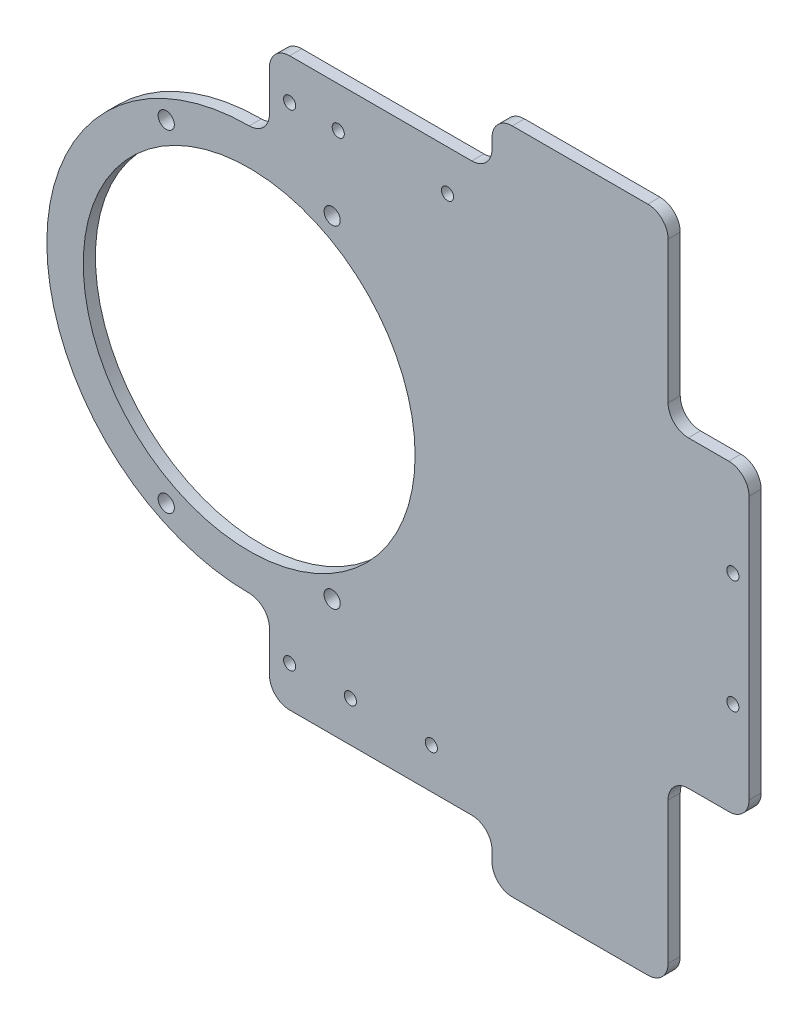
SolidWorks part; units mm, degrees
ref_plane "前视基准面" through (0, 0, 0) normal (0, 0, 1) x (1, 0, 0)
ref_plane "上视基准面" through (0, 0, 0) normal (0, 1, 0) x (1, 0, 0)
ref_plane "右视基准面" through (0, 0, 0) normal (1, 0, 0) x (0, 0, -1)
other "Configuration Table"
sketch "草图1" plane through (0, 0, 0) normal (0, 0, 1) x (1, 0, 0)
  line L1 (-55, 50) -> (55, 50)
  line L2 (-55, 50) -> (-55, -50)
  line L3 (-55, -50) -> (55, -50)
  line L4 (55, 50) -> (55, -50)
  line L5 (-55, 50) -> (55, -50) construction
  line L6 (-55, -50) -> (55, 50) construction
  line L7 (118.5, 82.5) -> (55, 82.5)
  line L8 (118.5, 82.5) -> (118.5, -82.5)
  line L9 (118.5, -82.5) -> (55, -82.5)
  line L10 (55, 82.5) -> (55, -82.5)
  line L11 (118.5, 82.5) -> (55, -82.5) construction
  line L12 (118.5, -82.5) -> (55, 82.5) construction
  line L21 (55, 50) -> (0, 50)
  line L22 (55, 50) -> (55, 70)
  line L23 (55, 70) -> (0, 70)
  line L24 (0, 50) -> (0, 70)
  line L25 (55, -50) -> (0, -50)
  line L26 (55, -50) -> (55, -70)
  line L27 (55, -70) -> (0, -70)
  line L28 (0, -50) -> (0, -70)
  point P0 (0, 0)
  point P6 (86.75, 0)
  dimension "D1" = 100
  dimension "D2" = 110
  dimension "D3" = 173.5
  dimension "D4" = 165
  dimension "D9" = 20
  dimension "D10" = 20
  dimension "D11" = 55
  dimension "D12" = 55
extrude "凸台-拉伸1" add sketch "草图1" along normal blind 3 contours L4 L1 L2 L3 | L7 L10 L4 L9 L8 | L8 | L8 | L24 L1 L10 L23 | L3 L28 L27 L10 region at (0, 0, 0) region at (27.5, 60, 0) region at (86.75, 0, 0) region at (27.5, -60, 0)
fillet "圆角1" radius 50 2 edges at (-55, -50, 1.5) (-55, 50, 1.5)
sketch "草图2" plane through (0, 0, 3) normal (0, 0, 1) x (1, 0, 0)
  circle A0 centre (-5, 0) radius 41
  dimension "D1" = 82
extrude "切除-拉伸1" cut sketch "草图2" against normal blind 10
fillet "圆角4" radius 5 6 edges at (0, 70, 1.5) (55, 70, 1.5) (55, -70, 1.5) (0, -70, 1.5) (0, -50, 1.5) (0, 50, 1.5)
sketch "草图3" plane through (0, 0, 3) normal (0, 0, 1) x (1, 0, 0)
  line L1 (0, -55) -> (0, -65) construction
  line L2 (-25.5, -41) -> (15.5, -41) construction
  line L3 (-25.5, -41) -> (-25.5, 41) construction
  line L4 (-25.5, 41) -> (15.5, 41) construction
  line L5 (15.5, -41) -> (15.5, 41) construction
  line L6 (-25.5, -41) -> (15.5, 41) construction
  line L7 (-25.5, 41) -> (15.5, -41) construction
  line L8 (50, -70) -> (5, -70) construction
  line L9 (0, 55) -> (0, 65) construction
  line L10 (50, 70) -> (5, 70) construction
  line L11 (118.5, 82.5) -> (118.5, -82.5) construction
  circle A0 centre (114.5, 14) radius 1.5
  circle A1 centre (114.5, -14) radius 1.5
  circle A2 centre (-5, 0) radius 41 construction
  circle A3 centre (-5, 0) radius 41 construction
  circle A4 centre (-25.5, 41) radius 2
  circle A5 centre (15.5, 41) radius 2
  circle A6 centre (15.5, -41) radius 2
  circle A7 centre (-25.5, -41) radius 2
  circle A8 centre (5, -60) radius 1.5
  circle A9 centre (20, -60) radius 1.5
  circle A10 centre (40, -60) radius 1.5
  circle A11 centre (5, 60) radius 1.5
  circle A12 centre (17, 60) radius 1.5
  circle A13 centre (44, 60) radius 1.5
  dimension "D3" = 3
  dimension "D4" = 3
  dimension "D8" = 4
  dimension "D9" = 4
  dimension "D10" = 4
  dimension "D11" = 4
  dimension "D12" = 3
  dimension "D13" = 3
  dimension "D14" = 3
  dimension "D22" = 3
  dimension "D23" = 3
  dimension "D24" = 3
  dimension "D25" = 10
  dimension "D1" = 28
  dimension "D5" = 14
  dimension "D6" = 82
  dimension "D7" = 41
  dimension "D15" = 5
  dimension "D16" = 15
  dimension "D17" = 20
  dimension "D18" = 10
  dimension "D19" = 5
  dimension "D20" = 12
  dimension "D21" = 27
  dimension "D26" = 4
extrude "切除-拉伸2" cut sketch "草图3" against normal blind 10
sketch "草图4" plane through (0, 0, 3) normal (0, 0, 1) x (1, 0, 0)
  line L1 (118.5, 82.5) -> (98.5, 82.5)
  line L2 (118.5, 82.5) -> (118.5, 37.5)
  line L3 (118.5, 37.5) -> (98.5, 37.5)
  line L4 (98.5, 82.5) -> (98.5, 37.5)
  line L5 (118.5, -82.5) -> (98.5, -82.5)
  line L6 (118.5, -82.5) -> (118.5, -37.5)
  line L7 (118.5, -37.5) -> (98.5, -37.5)
  line L8 (98.5, -82.5) -> (98.5, -37.5)
  dimension "D1" = 45
  dimension "D2" = 20
  dimension "D3" = 45
  dimension "D4" = 20
extrude "切除-拉伸3" cut sketch "草图4" against normal blind 10
fillet "圆角5" radius 5 8 edges at (98.5, 82.5, 1.5) (55, 82.5, 1.5) (55, -82.5, 1.5) (98.5, -37.5, 1.5) (118.5, -37.5, 1.5) (118.5, 37.5, 1.5) (98.5, 37.5, 1.5) (98.5, -82.5, 1.5)
